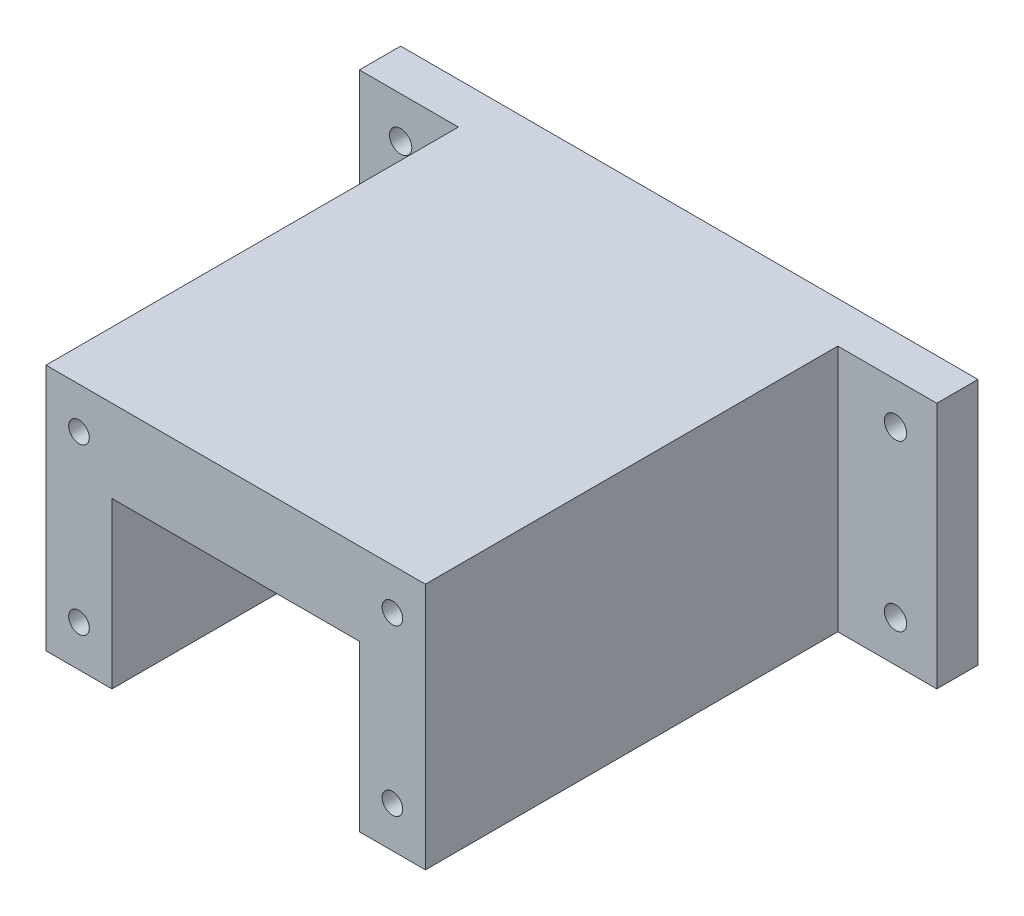
SolidWorks part; units mm, degrees
ref_plane "前基準面" through (0, 0, 0) normal (0, 0, 1) x (1, 0, 0)
ref_plane "上基準面" through (0, 0, 0) normal (0, 1, 0) x (1, 0, 0)
ref_plane "右基準面" through (0, 0, 0) normal (1, 0, 0) x (0, 0, -1)
ref_axis "基準軸1" through (0, -55, 0) along (0, 1, 0)
ref_axis "基準軸2" through (-88.99, 0, 0) along (1, 0, 0)
ref_axis "基準軸3" through (0, 0, 55) along (0, 0, -1)
sketch "草圖1" plane through (0, 0, 0) normal (0, 0, 1) x (1, 0, 0)
  line L0 (20, 0) -> (20, 10)
  line L1 (0, 0) -> (20, 0)
  line L2 (0, 0) -> (0, 30)
  line L3 (0, 30) -> (70, 30)
  line L4 (70, 0) -> (70, 30)
  line L5 (20, 10) -> (50, 10)
  line L6 (50, 10) -> (50, 0)
  line L7 (50, 0) -> (70, 0)
  circle A0 centre (5, 25) radius 1.35
  circle A1 centre (5, 5) radius 1.35
  circle A2 centre (65, 25) radius 1.35
  circle A3 centre (65, 5) radius 1.35
  dimension "D6" = 2.7
  dimension "D7" = 2.7
  dimension "D8" = 2.7
  dimension "D9" = 2.7
  dimension "D1" = 70
  dimension "D2" = 30
  dimension "D3" = 30
  dimension "D4" = 10
  dimension "D5" = 20
  dimension "D10" = 5
  dimension "D11" = 5
  dimension "D12" = 5
  dimension "D13" = 5
  dimension "D14" = 5
  dimension "D15" = 5
  dimension "D16" = 5
  dimension "D17" = 5
extrude "填料-伸長1" add sketch "草圖1" along normal blind 5
sketch "草圖2" plane through (0, 0, 5) normal (0, 0, 1) x (1, 0, 0)
  line L0 (20, 20) -> (20, 0)
  line L1 (2.75, 0) -> (-2.75, 0) construction
  line L2 (20, 0) -> (20, 10) construction
  line L3 (20, 0) -> (12, 0)
  line L4 (12, 0) -> (12, 30)
  line L5 (70, 30) -> (0, 30) construction
  line L6 (12, 30) -> (58, 30)
  line L7 (58, 30) -> (58, 0)
  line L8 (58, 0) -> (50, 0)
  line L9 (50, 0) -> (50, 20)
  line L10 (50, 20) -> (20, 20)
  dimension "D1" = 8
  dimension "D2" = 8
  dimension "D3" = 46
  dimension "D4" = 20
extrude "填料-伸長2" add sketch "草圖2" along normal blind 50
sketch "草圖3" plane through (0, 0, 55) normal (0, 0, 1) x (1, 0, 0)
  line L0 (58, 30) -> (12, 30) construction
  line L1 (12, 30) -> (12, 0) construction
  circle A0 centre (16, 25) radius 1.25
  dimension "D1" = 2.5
  dimension "D2" = 5
  dimension "D3" = 4
extrude "除料-伸長1" cut sketch "草圖3" against normal blind 10
ref_plane "平面1" through (35, 0, 0) normal (1, 0, 0) x (0, 0, -1)
mirror "鏡射1" about plane through (35, 0, 0) normal (1, 0, 0) of "除料-伸長1"
ref_plane "平面2" through (0, 15, 0) normal (0, 1, 0) x (1, 0, 0)
mirror "鏡射2" about plane through (0, 15, 0) normal (0, 1, 0) of "鏡射1"
